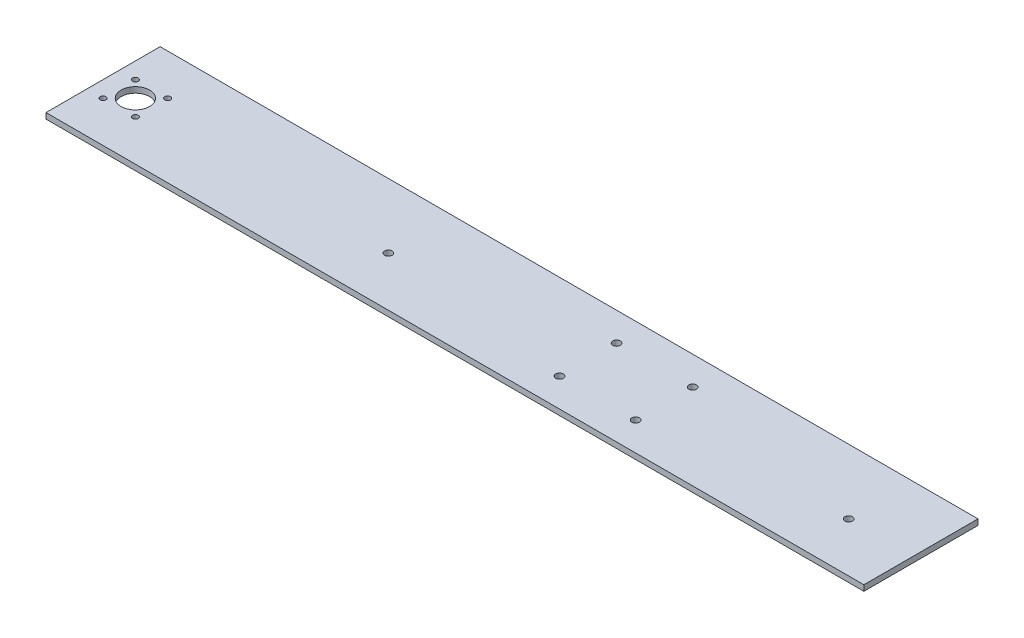
SolidWorks part; units mm, degrees
ref_plane "Płaszczyzna przednia" through (0, 0, 0) normal (0, 0, 1) x (1, 0, 0)
ref_plane "Płaszczyzna górna" through (0, 0, 0) normal (0, 1, 0) x (1, 0, 0)
ref_plane "Płaszczyzna prawa" through (0, 0, 0) normal (1, 0, 0) x (0, 0, -1)
sketch "Sketch1" plane through (0, 0, 0) normal (0, 1, 0) x (1, 0, 0)
  line L1 (-130, 0) -> (300, 0)
  line L2 (-130, 0) -> (-130, 60)
  line L3 (-130, 60) -> (300, 60)
  line L4 (300, 0) -> (300, 60)
  dimension "D1" = 430
  dimension "D2" = 60
extrude "Boss-Extrude1" add sketch "Sketch1" along normal blind 3
hole_wizard "Otwór pod śrubę M41" positions "Sketch2" profile "Sketch3" hole size "M4" standard "Ansi Metric" end condition through all
sketch "Sketch2" plane through (0, 3, 0) normal (0, 1, 0) x (1, 0, 0)
  line L0 (-130, 60) -> (-130, 0) construction
  line L1 (-130, 0) -> (300, 0) construction
  line L2 (300, 0) -> (300, 60) construction
  line L3 (300, 60) -> (-130, 60) construction
  point P0 (266, 26)
  point P2 (24, 26)
  point P20 (125, 15)
  point P22 (165, 15)
  point P24 (165, 45)
  point P26 (125, 45)
  dimension "D1" = 154
  dimension "D3" = 34
  dimension "D4" = 34
  dimension "D11" = 15
  dimension "D12" = 15
  dimension "D15" = 15
  dimension "D16" = 15
  dimension "D25" = 40
  dimension "D26" = 40
  dimension "D27" = 135
  dimension "D28" = 135
  dimension "D29" = 34
sketch "Sketch3" plane through (266, 3, -26) normal (1, 0, 0) x (0, 0, 1)
  line L0 (0, 0) -> (0, 3)
  line L1 (0, 3) -> (2, 3)
  line L2 (2, 3) -> (2, 0)
  line L5 (2, 0) -> (0, 0)
  line L11 (0, -6.35) -> (0, 107.95) construction
  dimension "Œrednica otworu na wylot" = 4
  dimension "G³êbokoœæ otworu na wylot" = 3
sketch "Sketch4" plane through (0, 3, 0) normal (0, 1, 0) x (1, 0, 0)
  line L0 (-130, 0) -> (300, 0) construction
  line L1 (-130, 60) -> (-130, 0) construction
  circle A0 centre (-113, 30) radius 7.5
  dimension "D1" = 15
  dimension "D2" = 30
  dimension "D3" = 17
extrude "Cut-Extrude1" cut sketch "Sketch4" against normal blind 5
hole_wizard "Ø3.0mm Dowel Hole1" positions "Sketch5" profile "Sketch6" hole size "Ø3.0" standard "ANSI Metric"
sketch "Sketch5" plane through (0, 3, 0) normal (0, 1, 0) x (1, 0, 0)
  point P0 (-121.4853, 21.5147)
  point P3 (-121.4853, 38.4853)
  point P6 (-104.5147, 21.5147)
  point P9 (-104.5147, 38.4853)
sketch "Sketch6" plane through (-121.4853, 3, -21.5147) normal (1, 0, 0) x (0, 0, 1)
  line L0 (0, 0) -> (0, 6.9013)
  line L1 (0, 6.9013) -> (1.5, 6)
  line L2 (1.5, 6) -> (1.5, 0)
  line L5 (1.5, 0) -> (0, 0)
  line L10 (0, 6.9013) -> (-1.5, 6) construction
  line L11 (0, -6.35) -> (0, 107.95) construction
  dimension "Hole Dia." = 3
  dimension "Hole Depth" = 6
  dimension "Drill Angle" = 118
